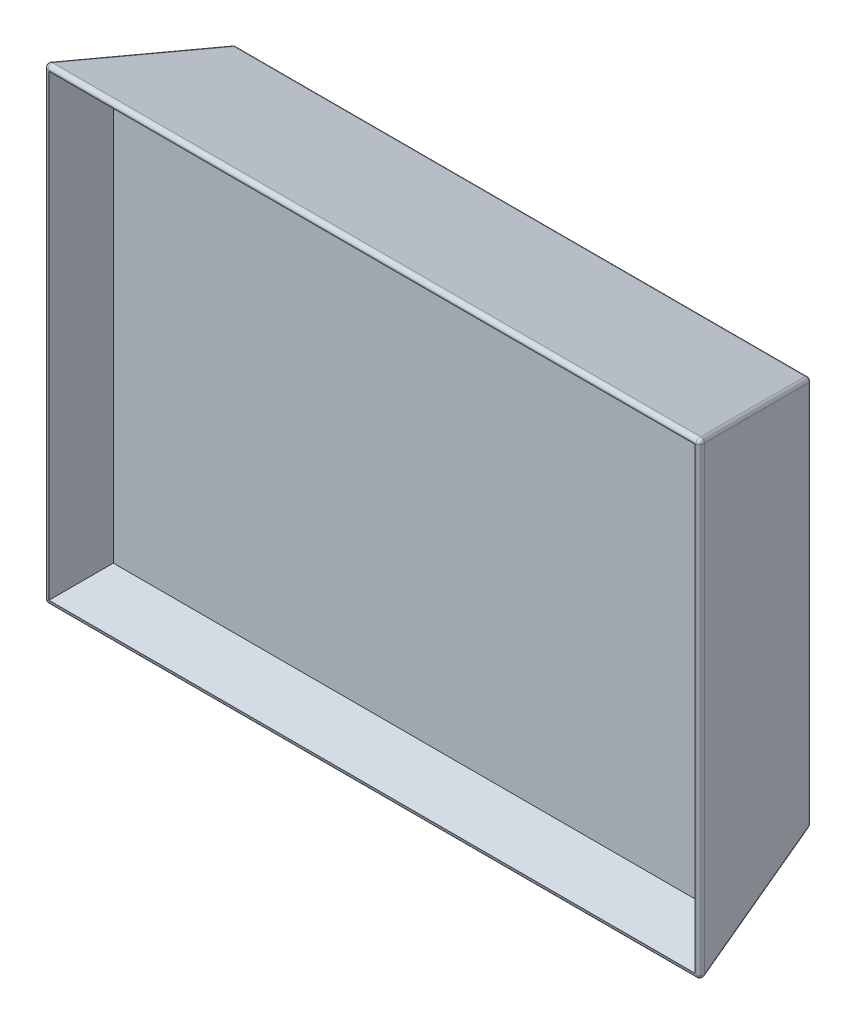
SolidWorks part; units mm, degrees
ref_plane "정면" through (0, 0, 0) normal (0, 0, 1) x (1, 0, 0)
ref_plane "윗면" through (0, 0, 0) normal (0, 1, 0) x (1, 0, 0)
ref_plane "우측면" through (0, 0, 0) normal (1, 0, 0) x (0, 0, -1)
sketch "스케치1" plane through (0, 0, 0) normal (0, 0, 1) x (1, 0, 0)
  line L1 (0, 0) -> (350, 0)
  line L2 (0, 0) -> (0, -250)
  line L3 (0, -250) -> (350, -250)
  line L4 (350, 0) -> (350, -250)
  dimension "D1" = 350
  dimension "D2" = 250
extrude "보스-돌출1" add sketch "스케치1" along normal blind 80 contours L1 L4 L3 L2
draft "구배3" type of draft neutral plane draft angle 15 faces to draft 4 face at (350, -125, 40) face at (175, -250, 40) face at (0, -125, 40) face at (175, 0, 40) neutral plane through (0, 0, 80) neutral plane normal (0, 0, 1) reverse direction yes parameters "D1"=15
fillet "필렛1" radius 2 12 edges at (0, -125, 80) (21.4359, -125, 0) (10.718, -239.282, 40) (175, -250, 80) (175, -228.5641, 0) (339.282, -239.282, 40) (350, -125, 80) (328.5641, -125, 0) (339.282, -10.718, 40) (175, 0, 80) (10.718, -10.718, 40) (175, -21.4359, 0)
shell "쉘8" thickness 3 removed face at (175, -125, 80)
ref_plane "평면1" through (0, 0, 53) normal (0, 0, 1) x (1, 0, 0)
sketch "스케치4" plane through (0, 0, 3) normal (0, 0, 1) x (1, 0, 0)
  line L0 (23.7379, -23.7379) -> (326.2621, -23.7379) construction
  line L1 (326.2621, -226.2621) -> (23.7379, -226.2621)
  line L2 (326.2621, -226.2621) -> (326.2621, -23.7379)
  line L3 (326.2621, -23.7379) -> (23.7379, -23.7379)
  line L4 (23.7379, -226.2621) -> (23.7379, -23.7379)
extrude "보스-돌출3" add sketch "스케치4" along normal blind 50 draft 15 separate body draft outward yes
